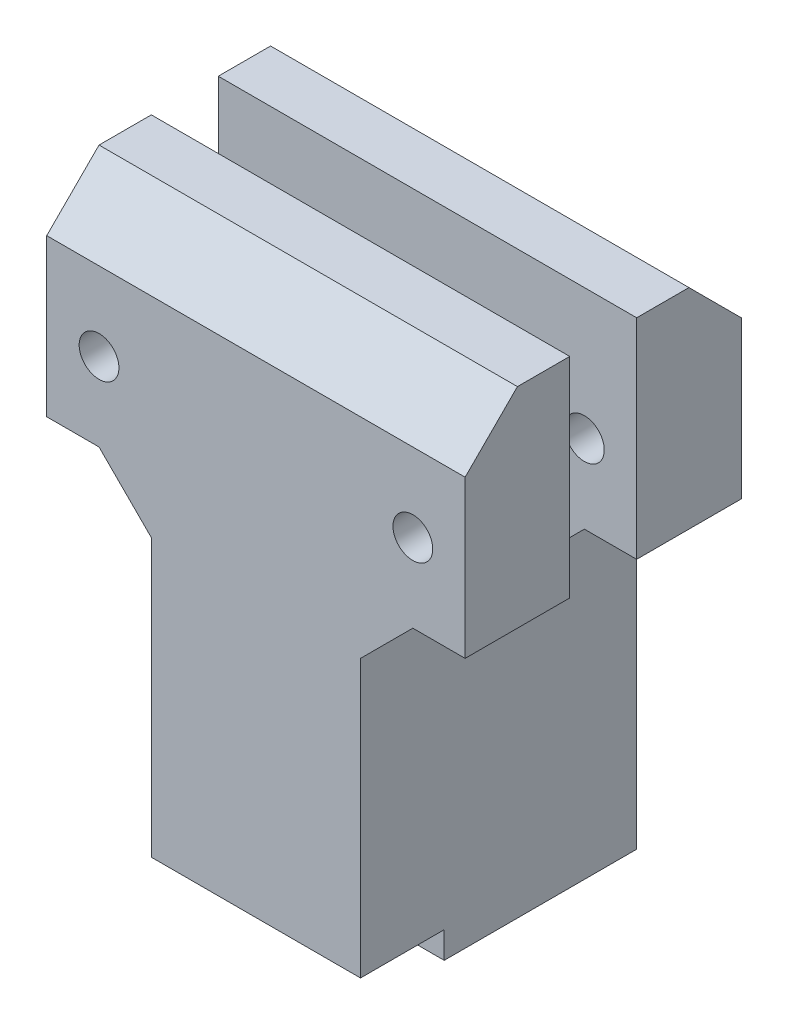
SolidWorks part; units mm, degrees
ref_plane "Front Plane" through (0, 0, 0) normal (0, 0, 1) x (1, 0, 0)
ref_plane "Top Plane" through (0, 0, 0) normal (0, 1, 0) x (1, 0, 0)
ref_plane "Right Plane" through (0, 0, 0) normal (1, 0, 0) x (0, 0, -1)
sketch "Sketch1" plane through (0, 0, 0) normal (0, 1, 0) x (1, 0, 0)
  line L1 (12.7, -16.764) -> (-12.7, -16.764)
  line L2 (12.7, -16.764) -> (12.7, 16.764)
  line L3 (12.7, 16.764) -> (-12.7, 16.764)
  line L4 (-12.7, -16.764) -> (-12.7, 16.764)
  line L5 (12.7, -16.764) -> (-12.7, 16.764) construction
  line L6 (12.7, 16.764) -> (-12.7, -16.764) construction
  line L7 (-12.7, 16.764) -> (12.7, 16.764)
  line L8 (-12.7, 16.764) -> (-12.7, 4.064)
  line L9 (-12.7, 4.064) -> (12.7, 4.064)
  line L10 (12.7, 16.764) -> (12.7, 4.064)
  line L11 (-12.7, -16.764) -> (12.7, -16.764)
  line L12 (-12.7, -16.764) -> (-12.7, -4.064)
  line L13 (-12.7, -4.064) -> (12.7, -4.064)
  line L14 (12.7, -16.764) -> (12.7, -4.064)
  point P0 (0, 0)
  dimension "D1" = 8.128
  dimension "D2" = 12.7
  dimension "D3" = 12.7
  dimension "D4" = 25.4
extrude "Boss-Extrude1" add sketch "Sketch1" along normal blind 25.4 contours L4 L9 L2 L3 | L13 L4 L1 L2 region at (0, 0, 10.414) region at (0, 0, -10.414)
extrude "Boss-Extrude2" add sketch "Sketch1<3>" against normal blind 43.1847 contours L4 L13 L2 L9 | L13 L4 L1 L2 | L4 L9 L2 L3 region at (0, 0, 10.414) region at (0, 0, 0) region at (0, 0, -10.414)
sketch "Sketch1<3>" plane through (0, 0, 0) normal (0, 1, 0) x (1, 0, 0) same geometry as "Sketch1"
sketch "Sketch2" plane through (0, 0, 16.764) normal (0, 0, 1) x (1, 0, 0)
  line L0 (12.7, -43.1847) -> (12.7, 25.4) construction
  line L1 (-12.7, -43.1847) -> (12.7, -43.1847)
  line L2 (-12.7, -43.1847) -> (-12.7, -39.9589)
  line L3 (-12.7, -39.9589) -> (12.7, -39.9589)
  line L4 (12.7, -43.1847) -> (12.7, -39.9589)
  dimension "D1" = 3.2258
extrude "Cut-Extrude1" cut sketch "Sketch2" against normal blind 10.16
chamfer "Chamfer1" distance 6.35 angle 45 2 edges at (0, 25.4, -16.764) (0, 25.4, 16.764)
sketch "Sketch4" plane through (0, 0, 16.764) normal (0, 0, 1) x (1, 0, 0)
  line L0 (12.7, -39.9589) -> (12.7, 19.05) construction
  line L1 (-12.7, 19.05) -> (12.7, 19.05)
  line L2 (-12.7, 19.05) -> (-12.7, 0)
  line L3 (-12.7, 0) -> (12.7, 0)
  line L4 (12.7, 19.05) -> (12.7, 0)
  line L5 (-12.7, 9.525) -> (12.7, 9.525)
  circle A0 centre (-6.35, 9.525) radius 2.413
  circle A1 centre (6.35, 9.525) radius 2.413
  dimension "D2" = 6.35
  dimension "D3" = 6.35
  dimension "D4" = 4.826
  dimension "D5" = 4.826
  dimension "D1" = 19.05
sketch "Sketch5" plane through (-12.7, 0, 0) normal (-1, 0, 0) x (0, 0, 1)
  line L0 (-16.764, 19.05) -> (-16.764, 0)
  line L1 (-16.764, 19.05) -> (-16.764, -43.1847) construction
  line L2 (-16.764, 0) -> (16.764, 0)
  line L3 (16.764, 19.05) -> (16.764, 0) construction
  line L4 (16.764, 0) -> (16.764, 19.05)
  line L5 (16.764, 19.05) -> (10.414, 25.4)
  line L6 (10.414, 25.4) -> (4.064, 25.4)
  line L7 (4.064, 25.4) -> (4.064, 0)
  line L8 (4.064, 0) -> (-4.064, 0)
  line L9 (-4.064, 0) -> (-4.064, 25.4)
  line L10 (-4.064, 25.4) -> (-10.414, 25.4)
  line L11 (-10.414, 25.4) -> (-16.764, 19.05)
  line M1 (-4.064, 25.4) -> (-10.414, 25.4)
  line M2 (-10.414, 25.4) -> (-16.764, 19.05)
  line M3 (-16.764, 19.05) -> (-16.764, -43.1847)
  line M7 (16.764, -39.9589) -> (16.764, 19.05)
  line M8 (16.764, 19.05) -> (10.414, 25.4)
  line M9 (10.414, 25.4) -> (4.064, 25.4)
  line M10 (4.064, 25.4) -> (4.064, 0)
  line M12 (-4.064, 0) -> (-4.064, 25.4)
extrude "Boss-Extrude3" add sketch "Sketch5" along normal blind 12.7 contours L2 M3 M12 M1 M2 | L2 M10 M7 M8 M9 region at (-12.7, 11.9944, -10.1318) region at (-12.7, 11.9944, 10.1318)
mirror "Mirror1" about plane through (0, 0, 0) normal (1, 0, 0) of "Boss-Extrude3"
sketch "Sketch6" plane through (0, 0, 16.764) normal (0, 0, 1) x (1, 0, 0)
  line L0 (-25.4, 9.525) -> (25.4, 9.525)
  line L1 (-25.4, 0) -> (-25.4, 19.05) construction
  line L2 (25.4, 0) -> (25.4, 19.05) construction
  circle A0 centre (-19.05, 9.525) radius 2.413
  circle A1 centre (19.05, 9.525) radius 2.413
  dimension "D1" = 6.35
  dimension "D2" = 6.35
  dimension "D3" = 4.826
  dimension "D4" = 4.826
extrude "Cut-Extrude3" cut sketch "Sketch6" against normal through all contours L0 A0 | L0 A0 | L0 A1 | L0 A1 region at (-19.05, 10.5491, 16.764) region at (19.05, 10.5491, 16.764) region at (19.05, 8.5009, 16.764) region at (-19.05, 8.5009, 16.764)
chamfer "Chamfer2" distance 6.35 angle 45 4 edges at (12.7, 0, -10.414) (12.7, 0, 10.414) (-12.7, 0, -10.414) (-12.7, 0, 10.414)
